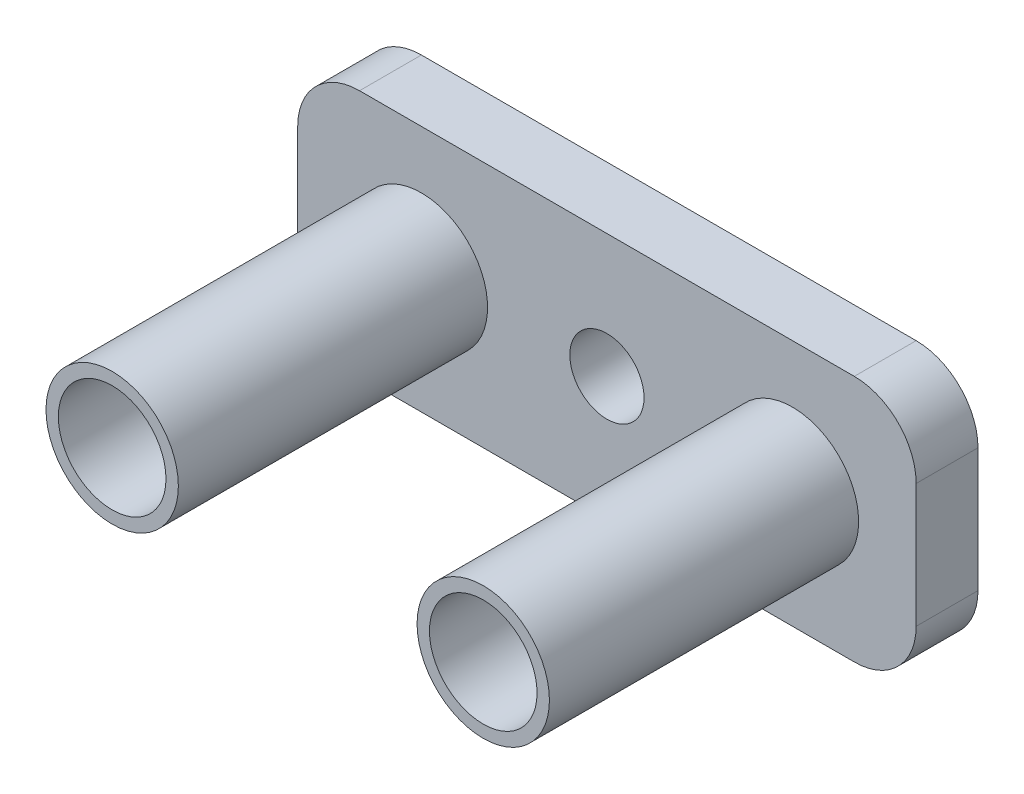
SolidWorks part; units mm, degrees
note: The reader was unsure of these and kept them because the rebuilt part matched: shared geometry of "Sketch1<7>", "Sketch1<8>".
ref_plane "Front Plane" through (0, 0, 0) normal (0, 0, 1) x (1, 0, 0)
ref_plane "Top Plane" through (0, 0, 0) normal (0, 1, 0) x (1, 0, 0)
ref_plane "Right Plane" through (0, 0, 0) normal (1, 0, 0) x (0, 0, -1)
sketch "Sketch1" plane through (0, 0, 0) normal (0, 0, 1) x (1, 0, 0)
  line L0 (-19.0299, -3.3769) -> (31.7109, -3.3769) construction
  line L1 (-14.0299, 6.6231) -> (25.9701, 6.6231)
  line L2 (-19.0299, 1.6231) -> (-19.0299, -8.3769)
  line L3 (-14.0299, -13.3769) -> (25.9701, -13.3769)
  line L4 (30.9701, 1.6231) -> (30.9701, -8.3769)
  line L5 (5.9701, 6.6231) -> (5.9701, -15.0107) construction
  arc A0 (-19.0299, 1.6231) -> (-14.0299, 6.6231) centre (-14.0299, 1.6231) cw
  arc A1 (30.9701, 1.6231) -> (25.9701, 6.6231) centre (25.9701, 1.6231) ccw
  arc A2 (25.9701, -13.3769) -> (30.9701, -8.3769) centre (25.9701, -8.3769) ccw
  arc A3 (-14.0299, -13.3769) -> (-19.0299, -8.3769) centre (-14.0299, -8.3769) cw
  circle A4 centre (-9.0299, -3.3769) radius 4.85
  circle A5 centre (20.9701, -3.3769) radius 4.85
  circle A6 centre (5.9701, -3.3769) radius 3
  point P6 (-19.0299, 6.6231)
  point P9 (30.9701, 6.6231)
  point P14 (-19.0299, -13.3769)
  dimension "D3" = 5
  dimension "D4" = 5
  dimension "D5" = 5
  dimension "D6" = 5
  dimension "D7" = 9.7
  dimension "D8" = 10
  dimension "D10" = 9.7
  dimension "D11" = 6
  dimension "D1" = 50
  dimension "D2" = 20
  dimension "D9" = 10
extrude "Boss-Extrude5" add sketch "Sketch1" along normal blind 5
extrude "Boss-Extrude6" add sketch "Sketch1<7>" along normal blind 5 contours L0 A4 | A4 L0 | A5
sketch "Sketch1<7>" plane through (0, 0, 0) normal (0, 0, 1) x (1, 0, 0) same geometry as "Sketch1"
extrude "Extrude-Thin1" add sketch "Sketch1<8>" along normal blind 30 thin contours L0 A4 | A4 L0 | L0 A5 | A5 L0
sketch "Sketch1<8>" plane through (0, 0, 0) normal (0, 0, 1) x (1, 0, 0) same geometry as "Sketch1"
